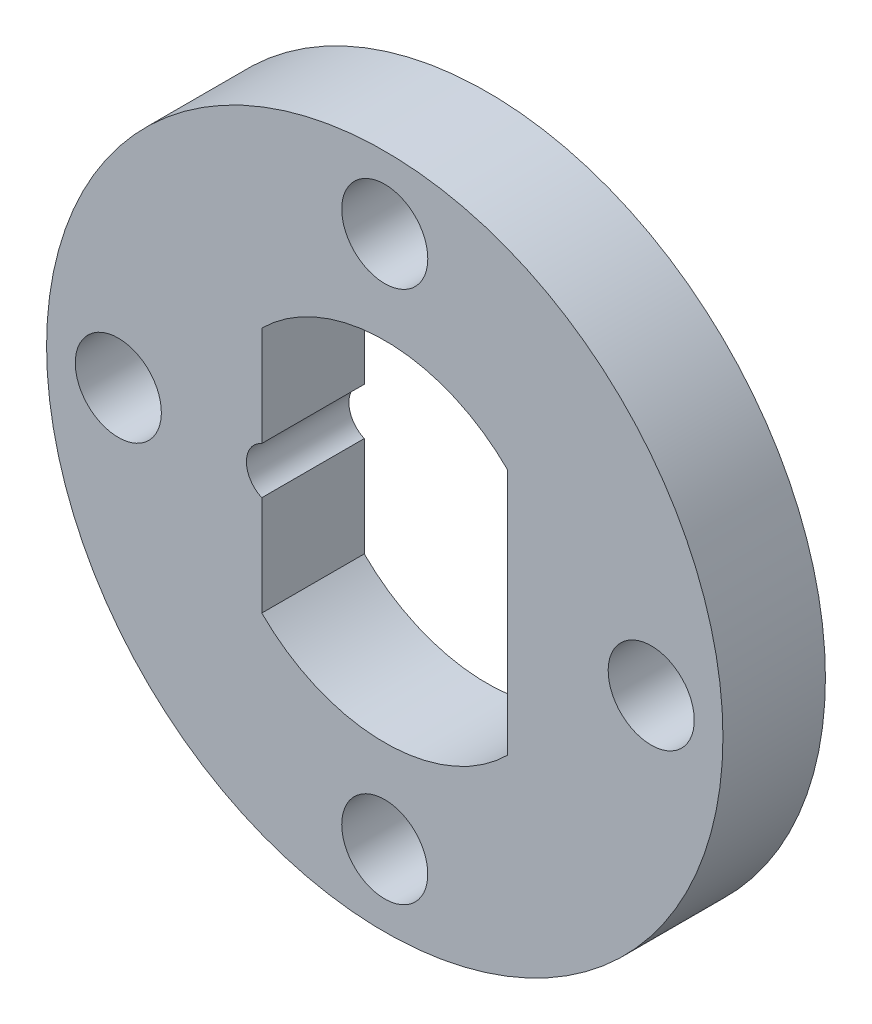
SolidWorks part; units mm, degrees
ref_plane "Plan de face" through (0, 0, 0) normal (0, 0, 1) x (1, 0, 0)
ref_plane "Plan de dessus" through (0, 0, 0) normal (0, 1, 0) x (1, 0, 0)
ref_plane "Plan de droite" through (0, 0, 0) normal (1, 0, 0) x (0, 0, -1)
sketch "Esquisse1" plane through (0, 0, 0) normal (0, 0, 1) x (1, 0, 0)
  line L0 (-6, 6.0208) -> (-6, -6.0208)
  line L1 (6, 6.0208) -> (6, -6.0208)
  line L2 (0, 1.129) -> (0, 12.3285) construction
  circle A0 centre (0, 0) radius 16.5
  arc A1 (6, 6.0208) -> (-6, 6.0208) centre (0, 0) ccw
  arc A2 (-6, -6.0208) -> (6, -6.0208) centre (0, 0) ccw
  dimension "D1" = 33
  dimension "D2" = 17
  dimension "D3" = 12
extrude "Extrusion1" add sketch "Esquisse1" along normal blind 5
sketch "Esquisse2" plane through (0, 0, 5) normal (0, 0, 1) x (1, 0, 0)
  line L0 (0, 0) -> (0, 14.1758) construction
  circle A0 centre (0, 13) radius 2.1
  dimension "D1" = 4.2
  dimension "D2" = 13
extrude "Enlèv. mat.-Extru.1" cut sketch "Esquisse2" against normal through all
ref_axis "Axe1" through (0, 0, 5) along (0, 0, -1)
pattern_circular "Répétition circulaire1" count 4 over 360 about axis through (0, 0, 5) along (0, 0, -1) of "Enlèv. mat.-Extru.1"
sketch "Esquisse3" plane through (0, 0, 5) normal (0, 0, 1) x (1, 0, 0)
  line L0 (0, 0) -> (-9.8933, 0) construction
  line L1 (-6, 6.0208) -> (-6, -6.0208) construction
  circle A0 centre (-5.5, 0) radius 1.25
  dimension "D1" = 2.5
  dimension "D2" = 0.5
extrude "Enlèv. mat.-Extru.2" cut sketch "Esquisse3" against normal through all
